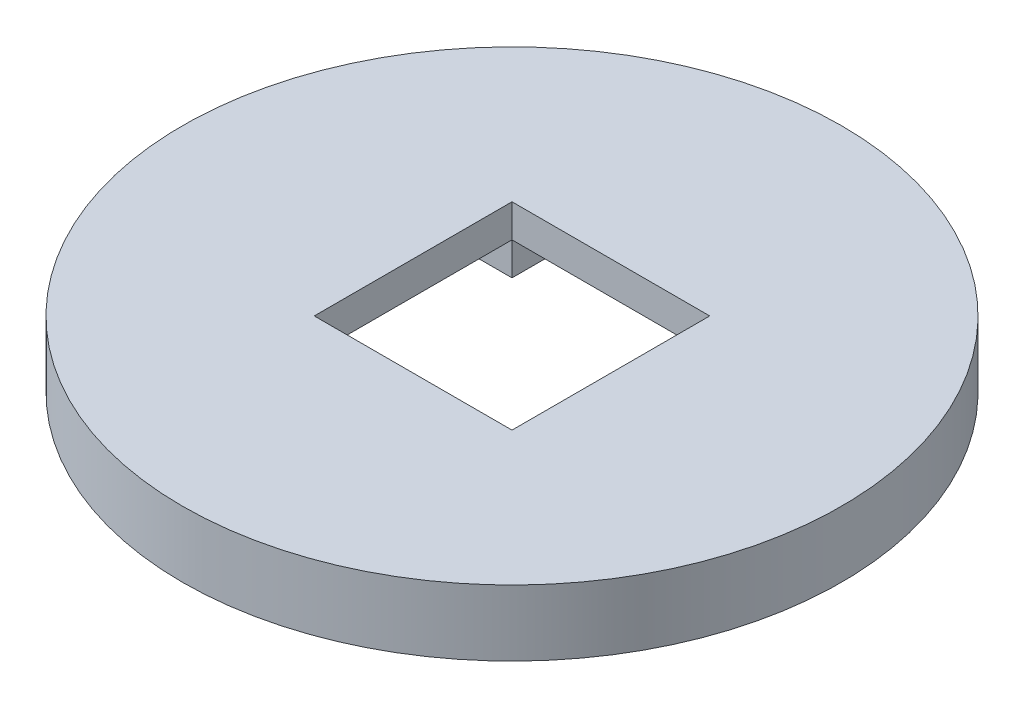
SolidWorks part; units mm, degrees
ref_plane "Front Plane" through (0, 0, 0) normal (0, 0, 1) x (1, 0, 0)
ref_plane "Top Plane" through (0, 0, 0) normal (0, 1, 0) x (1, 0, 0)
ref_plane "Right Plane" through (0, 0, 0) normal (1, 0, 0) x (0, 0, -1)
sketch "Sketch2" plane through (0, 0, 0) normal (0, 1, 0) x (1, 0, 0)
  circle A0 centre (0, 0) radius 50
  dimension "D1" = 100
extrude "Boss-Extrude1" add sketch "Sketch2" along normal blind 10 contours A0
sketch "Sketch4" plane through (0, 0, 0) normal (0, -1, 0) x (1, 0, 0)
  line L1 (-15, 30) -> (15, 30)
  line L2 (-15, 30) -> (-15, -30)
  line L3 (-15, -30) -> (15, -30)
  line L4 (15, 30) -> (15, -30)
  line L5 (-30, 15) -> (30, 15)
  line L6 (-30, 15) -> (-30, -15)
  line L7 (-30, -15) -> (30, -15)
  line L8 (30, 15) -> (30, -15)
  dimension "D1" = 30
  dimension "D2" = 15
  dimension "D3" = 15
  dimension "D4" = 30
  dimension "D5" = 30
  dimension "D6" = 30
  dimension "D7" = 15
  dimension "D8" = 15
extrude "Cut-Extrude4" cut sketch "Sketch4" against normal through all contours L2 L7 L4 L5 region at (0, 0, 0)
extrude "Cut-Extrude5" cut sketch "Sketch4<5>" against normal blind 5 contours L6 L7 L2 L5 | L7 L2 L3 L4 | L8 L5 L4 L7 | L2 L5 L4 L1 region at (0, 0, 22.5) region at (-22.5, 0, 0) region at (22.5, 0, 0) region at (0, 0, -22.5)
sketch "Sketch4<5>" plane through (0, 0, 0) normal (0, -1, 0) x (1, 0, 0) same geometry as "Sketch4"
